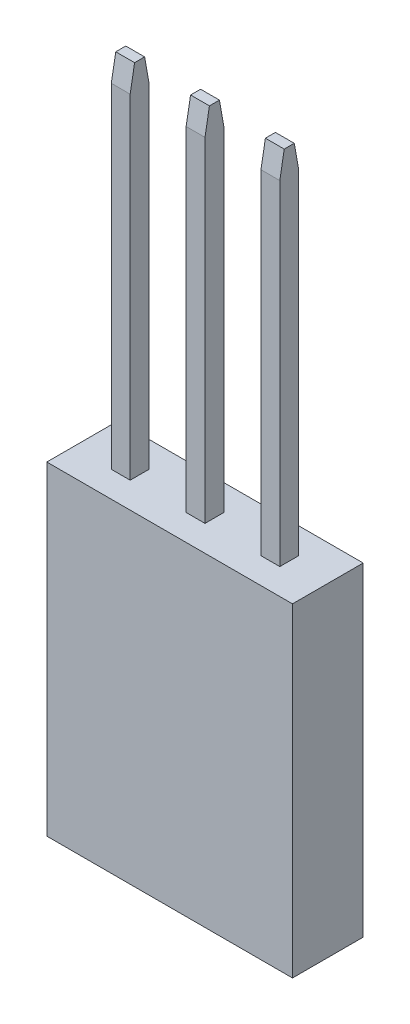
SolidWorks part; units mm, degrees
ref_plane "Front Plane" through (0, 0, 0) normal (0, 0, 1) x (1, 0, 0)
ref_plane "Top Plane" through (0, 0, 0) normal (0, 1, 0) x (1, 0, 0)
ref_plane "Right Plane" through (0, 0, 0) normal (1, 0, 0) x (0, 0, -1)
sketch "Sketch1" plane through (0, 0, 0) normal (0, 1, 0) x (1, 0, 0)
  line L0 (-2.54, 0) -> (2.54, 0) construction
  line L1 (-4.17, 1.2) -> (4.17, 1.2)
  line L2 (-4.17, 1.2) -> (-4.17, -1.2)
  line L3 (-4.17, -1.2) -> (4.17, -1.2)
  line L4 (4.17, 1.2) -> (4.17, -1.2)
  point P4 (0, -1.2)
  point P6 (4.17, 0)
  point P7 (-2.54, 0)
  point P8 (0, 0)
  point P9 (2.54, 0)
  dimension "D1" = 2.4
  dimension "D2" = 2.54
  dimension "D3" = 8.34
extrude "Boss-Extrude1" add sketch "Sketch1" against normal blind 11
sketch "Sketch2" plane through (0, 0, 0) normal (0, 1, 0) x (1, 0, 0)
  line L0 (0, 0.32) -> (0, -0.32) construction
  line L1 (-0.32, 0.32) -> (0.32, 0.32)
  line L2 (-0.32, 0.32) -> (-0.32, -0.32)
  line L3 (-0.32, -0.32) -> (0.32, -0.32)
  line L4 (0.32, 0.32) -> (0.32, -0.32)
  line L5 (-2.86, 0.32) -> (-2.22, 0.32)
  line L6 (-2.86, 0.32) -> (-2.86, -0.32)
  line L7 (-2.86, -0.32) -> (-2.22, -0.32)
  line L8 (-2.22, 0.32) -> (-2.22, -0.32)
  line L9 (2.22, 0.32) -> (2.22, -0.32)
  line L10 (2.86, -0.32) -> (2.22, -0.32)
  line L11 (2.86, 0.32) -> (2.86, -0.32)
  line L12 (2.86, 0.32) -> (2.22, 0.32)
  point P4 (0.32, 0)
  point P6 (0, 0.32)
  point P11 (-2.54, 0.32)
  point P13 (-2.22, 0)
  dimension "D1" = 0.64
  dimension "D2" = 0.64
extrude "Boss-Extrude2" add sketch "Sketch2" along normal blind 12.2 separate body
chamfer "Chamfer1" distance 0.15 angle 80 2 edges at (-2.54, 12.2, -0.32) (-2.54, 12.2, 0.32) first distance on face at (-2.54, 12.2, 0)
chamfer "Chamfer2" distance 0.15 angle 80 2 edges at (0, 12.2, -0.32) (0, 12.2, 0.32) first distance on face at (0, 12.2, 0)
chamfer "Chamfer3" distance 0.15 angle 80 2 edges at (2.54, 12.2, -0.32) (2.54, 12.2, 0.32) first distance on face at (2.54, 12.2, 0)
extrude "Cut-Extrude1" cut sketch "Sketch2<2>" along normal blind 4 from surface starting at face at (0, -11, 0)
sketch "Sketch2<2>" plane through (0, 0, 0) normal (0, 1, 0) x (1, 0, 0) same geometry as "Sketch2"
chamfer "Chamfer4" distance 0.3 angle 45 12 edges at (-2.54, -11, -0.32) (-2.22, -11, 0) (-2.54, -11, 0.32) (-2.86, -11, 0) (0.32, -11, 0) (0, -11, -0.32) (-0.32, -11, 0) (0, -11, 0.32) (2.86, -11, 0) (2.54, -11, -0.32) (2.22, -11, 0) (2.54, -11, 0.32)
